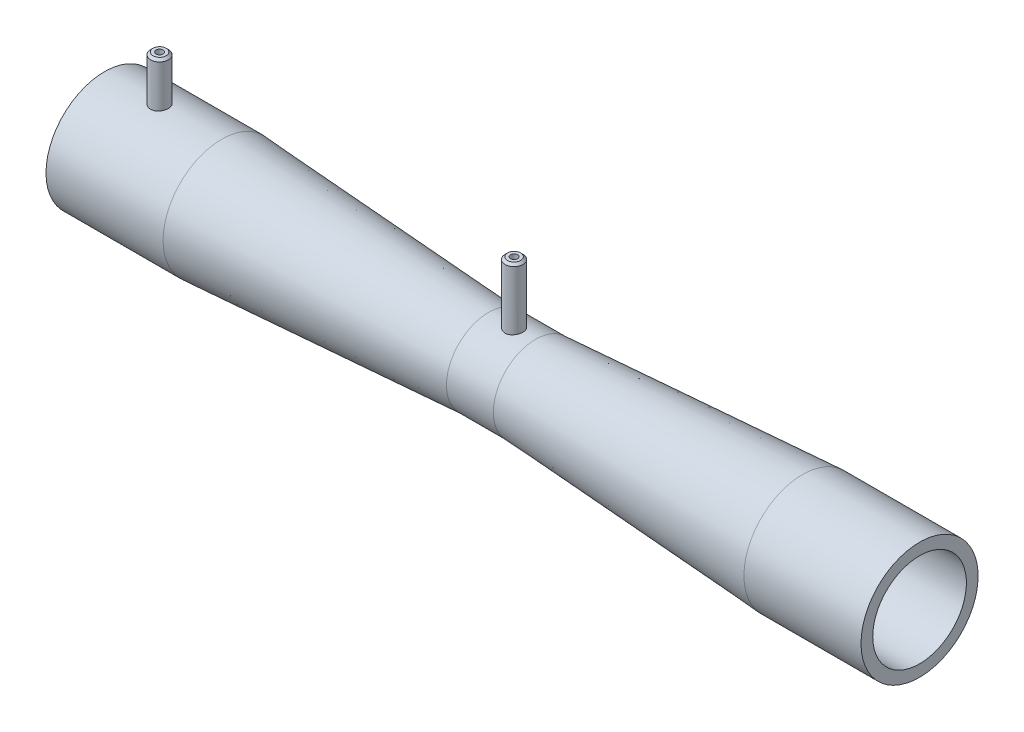
SolidWorks part; units mm, degrees
ref_plane "Front Plane" through (0, 0, 0) normal (0, 0, 1) x (1, 0, 0)
ref_plane "Top Plane" through (0, 0, 0) normal (0, 1, 0) x (1, 0, 0)
ref_plane "Right Plane" through (0, 0, 0) normal (1, 0, 0) x (0, 0, -1)
sketch "Sketch6" plane through (0, 0, 0) normal (0, 0, 1) x (1, 0, 0)
  line L0 (0, 0) -> (174, 0) construction
  line L1 (0.5611, 12.5) -> (25.5611, 12.5)
  line L2 (25.5611, 12.5) -> (82.5611, 9)
  line L3 (82.5611, 9) -> (92.5611, 9)
  line L4 (149.5611, 12.5) -> (92.5611, 9)
  line L5 (149.5611, 12.5) -> (174.5611, 12.5)
  line L6 (0.5611, 10) -> (25.4844, 10)
  line L7 (25.4844, 10) -> (82.4844, 6.5)
  line L8 (82.4844, 6.5) -> (92.6377, 6.5)
  line L9 (149.6377, 10) -> (92.6377, 6.5)
  line L10 (149.6377, 10) -> (174.5611, 10)
  line L11 (0.5611, 12.5) -> (0.5611, 10)
  line L12 (174.5611, 12.5) -> (174.5611, 10)
  dimension "D1" = 174
  dimension "D2" = 25
  dimension "D3" = 12.5
  dimension "D4" = 57
  dimension "D5" = 6.5
  dimension "D6" = 10
  dimension "D7" = 57
  dimension "D8" = 25
  dimension "D9" = 12.5
  dimension "D10" = 2.5
revolve "Revolve1" add sketch "Sketch6" angle 360 about L0
ref_plane "Plane1" through (0, 22, 0) normal (0, 1, 0) x (1, 0, 0)
sketch "Sketch14" plane through (0, 22, 0) normal (0, 1, 0) x (1, 0, 0)
  line L0 (0.5611, 0) -> (87.9966, 0)
  line L2 (0.5611, 12.5) -> (0.5611, -12.5) construction
  circle A0 centre (12.3034, 0) radius 1.9
  circle A1 centre (87.9966, 0) radius 1.9
  dimension "D1" = 3.8
  dimension "D2" = 3.8
extrude "Boss-Extrude7" add sketch "Sketch14" against normal up to body contours A1 | A0 region at (87.9966, 22, -1.8463)
sketch "Sketch15" plane through (0, 22, 0) normal (0, 1, 0) x (1, 0, 0)
  circle A0 centre (12.3034, 0) radius 0.75
  circle A1 centre (87.9966, 0) radius 0.75
  dimension "D1" = 1.5
  dimension "D2" = 1.5
extrude "Cut-Extrude6" cut sketch "Sketch15" against normal blind 19.75
chamfer "Chamfer2" distance 0.5 angle 45 2 edges at (12.3034, 22, 1.9) (87.9966, 22, 1.9)
fillet "Fillet3" radius 1 2 edges at (87.8297, 6.4587, -0.7312) (12.1333, 9.9733, -0.7304)
sketch "Sketch16" plane through (0.5611, 0, 0) normal (-1, 0, 0) x (0, 0, 1)
  circle A0 centre (0, 0) radius 10
sketch "Sketch17" plane through (174.5611, 0, 0) normal (1, 0, 0) x (0, 0, -1)
  circle A0 centre (0, 0) radius 10
sketch "Sketch18" plane through (0, 22, 0) normal (0, 1, 0) x (1, 0, 0)
  circle A0 centre (87.9966, 0) radius 0.75
sketch "Sketch21" plane through (0, 22, 0) normal (0, 1, 0) x (1, 0, 0)
  circle A0 centre (12.3034, 0) radius 0.7592
